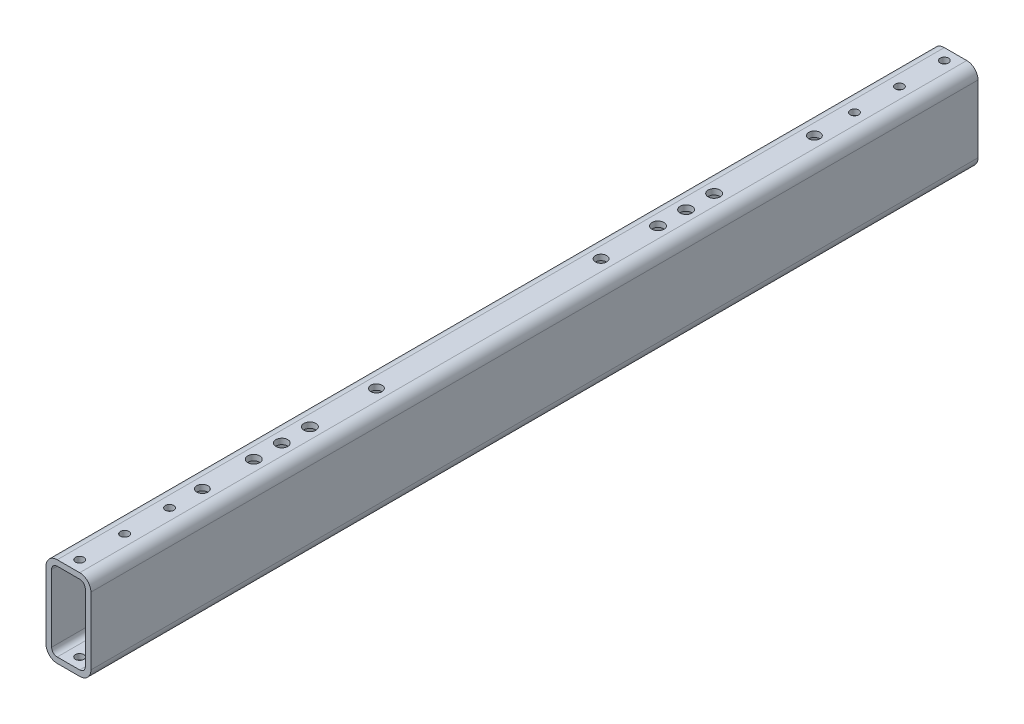
SolidWorks part; units mm, degrees
material "6061-T6 (SS)"
ref_plane "Front Plane" through (0, 0, 0) normal (0, 0, 1) x (1, 0, 0)
ref_plane "Top Plane" through (0, 0, 0) normal (0, 1, 0) x (1, 0, 0)
ref_plane "Right Plane" through (0, 0, 0) normal (1, 0, 0) x (0, 0, -1)
sketch "Sketch1" plane through (0, 0, 0) normal (0, 0, 1) x (1, 0, 0)
  line L1 (-6.35, -25.4) -> (6.35, -25.4)
  line L2 (-12.7, -19.05) -> (-12.7, 19.05)
  line L3 (-6.35, 25.4) -> (6.35, 25.4)
  line L4 (12.7, -19.05) -> (12.7, 19.05)
  line L5 (-12.7, -25.4) -> (12.7, 25.4) construction
  line L6 (-12.7, 25.4) -> (12.7, -25.4) construction
  arc A0 (-12.7, -19.05) -> (-6.35, -25.4) centre (-6.35, -19.05) ccw
  arc A1 (6.35, -25.4) -> (12.7, -19.05) centre (6.35, -19.05) ccw
  arc A2 (6.35, 25.4) -> (12.7, 19.05) centre (6.35, 19.05) cw
  arc A3 (-12.7, 19.05) -> (-6.35, 25.4) centre (-6.35, 19.05) cw
  point P0 (0, 0)
  dimension "D3" = 6.35
  dimension "D1" = 50.8
  dimension "D2" = 25.4
extrude "Extrude-Thin1" add sketch "Sketch1" along normal blind 501.65 thin thin type one direction reverse wall 3.175
hole_wizard "3/16 (0.1875) Diameter Hole1" positions "3DSketch1" profile "Sketch3" hole size "3/16" standard "ANSI Inch" end condition through all
sketch3d "3DSketch1"
  line L1 (6.35, 25.4, 0) -> (-6.35, 25.4, 0) construction
  line L6 (0, 25.4, 501.65) -> (0, 25.4, 0) construction
  line L7 (6.35, 25.4, 501.65) -> (-6.35, 25.4, 501.65) construction
  point P57 (0, 25.4, 6.35)
  point P59 (0, 25.4, 31.75)
  point P61 (0, 25.4, 57.15)
  point P63 (0, 25.4, 469.9)
  point P65 (0, 25.4, 444.5)
  point P67 (0, 25.4, 495.3)
  dimension "D1" = 25.4
  dimension "D2" = 25.4
  dimension "D3" = 6.35
  dimension "D4" = 25.4
  dimension "D5" = 25.4
  dimension "D6" = 6.35
sketch "Sketch3" plane through (0, 25.4, 495.3) normal (1, 0, 0) x (0, 0, 1)
  line L0 (0, 0) -> (0, 50.8)
  line L1 (0, 50.8) -> (2.3812, 50.8)
  line L2 (2.3812, 50.8) -> (2.3812, 0)
  line L5 (2.3812, 0) -> (0, 0)
  line L11 (0, -6.35) -> (0, 107.95) construction
  dimension "Thru Hole Dia." = 4.7625
  dimension "Thru Hole Depth" = 50.8
hole_wizard "3/16 (0.195) Diameter Hole1" positions "Sketch4" profile "Sketch5" hole size "3/16" standard "ANSI Inch" end condition up to next
sketch "Sketch4" plane through (0, -25.4, 0) normal (0, -1, 0) x (-1, 0, 0)
  point P28 (3.175, -85.7193)
  point P31 (-3.175, -111.1193)
  point P34 (3.175, -136.5193)
  point P37 (-3.175, -161.9193)
  point P40 (3.175, -187.3193)
  point P43 (3.175, -339.7193)
  point P46 (-3.175, -365.1193)
  point P49 (3.175, -390.5193)
  point P52 (-3.175, -415.9193)
  point P60 (-3.175, -212.7193)
  point P63 (3.175, -238.1193)
  point P66 (-3.175, -263.5193)
  point P69 (3.175, -288.9193)
  point P72 (-3.175, -314.3193)
sketch "Sketch5" plane through (-3.175, -25.4, 85.7193) normal (1, 0, 0) x (0, 0, -1)
  line L0 (0, 0) -> (0, 3.175)
  line L1 (0, 3.175) -> (2.4765, 3.175)
  line L2 (2.4765, 3.175) -> (2.4765, 0)
  line L5 (2.4765, 0) -> (0, 0)
  line L11 (0, -6.35) -> (0, 107.95) construction
  dimension "Thru Hole Dia." = 4.953
  dimension "Thru Hole Depth" = 3.175
hole_wizard "1/4 (0.25) Diameter Hole1" positions "Sketch7" profile "Sketch6" hole size "1/4" standard "ANSI Inch"
sketch "Sketch7" plane through (0, 25.4, 0) normal (0, 1, 0) x (1, 0, 0)
  point P6 (0, -79.831)
  point P9 (0, -425.9339)
  point P23 (0, -327.499)
  point P26 (0, -200.481)
sketch "Sketch6" plane through (0, 25.4, 79.831) normal (1, 0, 0) x (0, 0, 1)
  line L0 (0, 0) -> (0, 27.3077)
  line L1 (0, 27.3077) -> (3.175, 25.4)
  line L2 (3.175, 25.4) -> (3.175, 0)
  line L5 (3.175, 0) -> (0, 0)
  line L10 (0, 27.3077) -> (-3.175, 25.4) construction
  line L11 (0, -6.35) -> (0, 107.95) construction
  dimension "Hole Dia." = 6.35
  dimension "Hole Depth" = 25.4
  dimension "Drill Angle" = 118
hole_wizard "1/4 Clearance Hole1" positions "Sketch8" profile "Sketch9" hole size "1/4" standard "ANSI Inch"
sketch "Sketch8" plane through (381, 25.4, 250.825) normal (0, 1, 0) x (1, 0, 0)
  point P0 (381, 82.55)
  point P3 (381, 98.425)
  point P6 (381, 114.3)
  point P9 (381, -146.05)
  point P12 (381, -130.175)
  point P15 (381, -114.3)
  point P18 (-381, -146.05)
  point P21 (-381, -130.175)
  point P24 (-381, -114.3)
  point P27 (-381, 82.55)
  point P30 (-381, 98.425)
  point P33 (-381, 114.3)
sketch "Sketch9" plane through (762, 25.4, 168.275) normal (1, 0, 0) x (0, 0, 1)
  line L0 (0, 0) -> (0, 8.3798)
  line L1 (0, 8.3798) -> (3.3782, 6.35)
  line L2 (3.3782, 6.35) -> (3.3782, 0)
  line L3 (3.3782, 0) -> (0, 0)
  line L4 (0, 8.3798) -> (-3.3782, 6.35) construction
  line L5 (0, -6.35) -> (0, 107.95) construction
  dimension "Hole Dia." = 6.7564
  dimension "Hole Depth" = 6.35
  dimension "Drill Angle" = 118
